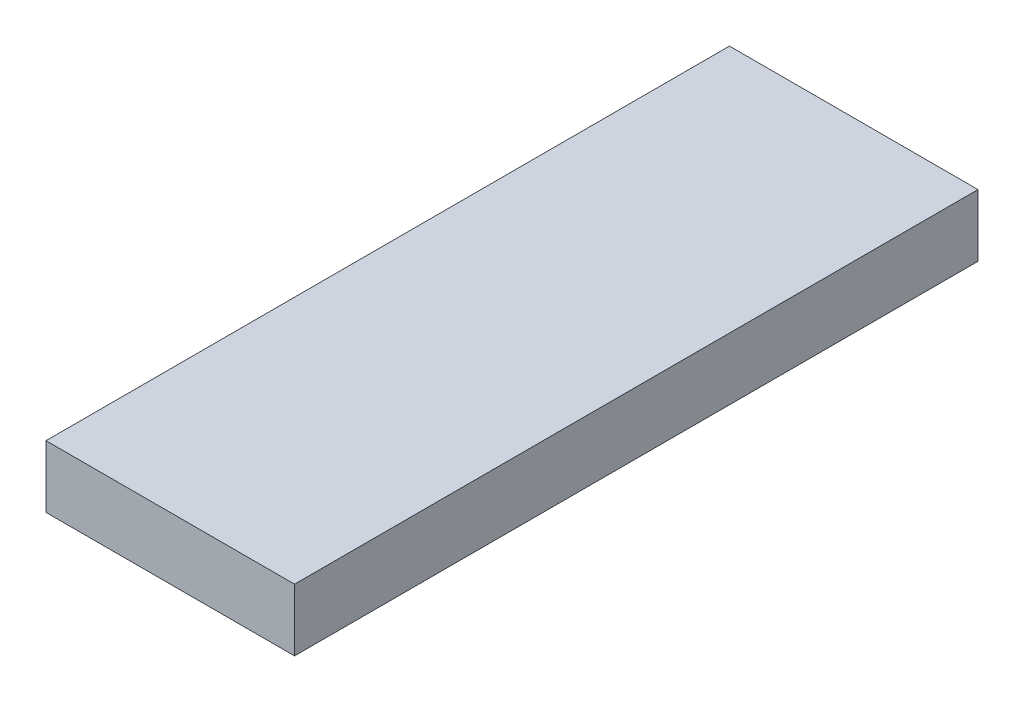
SolidWorks part; units mm, degrees
material "Maple"
ref_plane "Front Plane" through (0, 0, 0) normal (0, 0, 1) x (1, 0, 0)
ref_plane "Top Plane" through (0, 0, 0) normal (0, 1, 0) x (1, 0, 0)
ref_plane "Right Plane" through (0, 0, 0) normal (1, 0, 0) x (0, 0, -1)
sketch "Sketch1" plane through (0, 0, 0) normal (0, 1, 0) x (1, 0, 0)
  line L0 (0, 0) -> (50.8, 0)
  line L1 (0, 0) -> (0, 139.7)
  line L2 (50.8, 0) -> (50.8, 139.7)
  line L3 (0, 139.7) -> (50.8, 139.7)
  dimension "D1" = 50.8
  dimension "D2" = 139.7
extrude "Boss-Extrude1" add sketch "Sketch1" along normal blind 12.7
